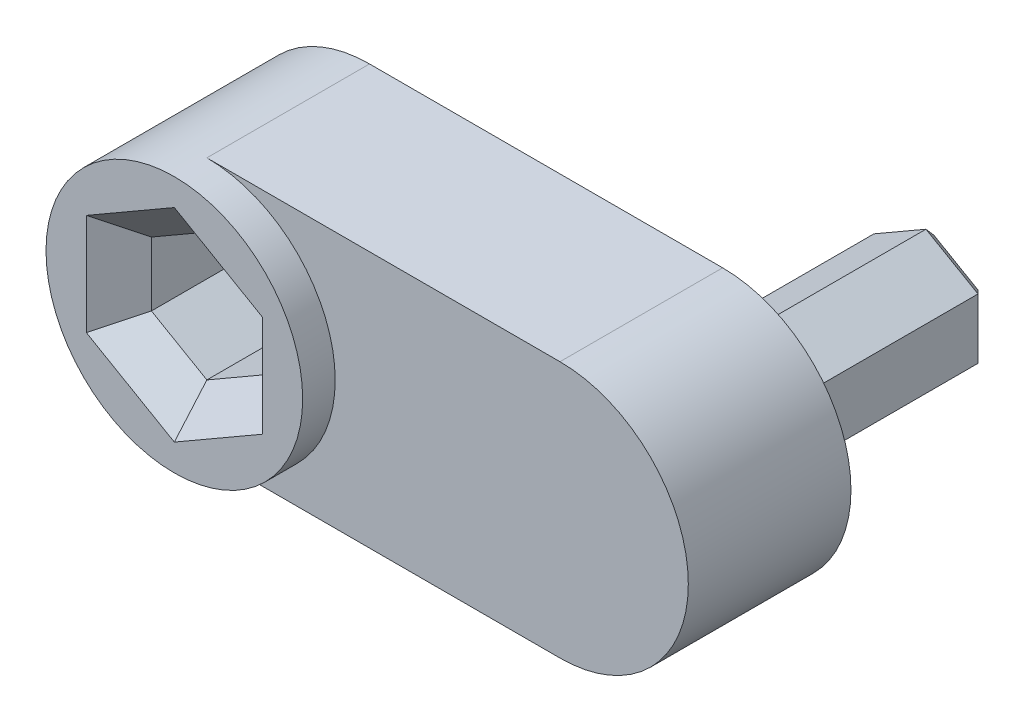
SolidWorks part; units mm, degrees
ref_plane "Plan de face" through (0, 0, 0) normal (1, 0, 0) x (0, 1, 0)
ref_plane "Plan de dessus" through (0, 0, 0) normal (0, 0, 1) x (0, 1, 0)
ref_plane "Plan de droite" through (0, 0, 0) normal (0, 1, 0) x (-1, 0, 0)
sketch "Esquisse1" plane through (0, 0, 0) normal (0, 0, 1) x (0, 1, 0)
  line L0 (0, -10.855) -> (0, 10.855) construction
  line L1 (-7.89, -10.855) -> (-7.89, 10.855)
  line L2 (7.89, -10.855) -> (7.89, 10.855)
  arc A0 (-7.89, -10.855) -> (7.89, -10.855) centre (0, -10.855) ccw
  arc A1 (7.89, 10.855) -> (-7.89, 10.855) centre (0, 10.855) ccw
  point P2 (0, 0)
  dimension "D2" = 15.78
  dimension "D1" = 21.71
extrude "Boss.-Extru.1" add sketch "Esquisse1" along normal blind 10
sketch "Esquisse3" plane through (0, 0, 0) normal (0, 0, -1) x (1, 0, 0)
  line L1 (10.855, -3.695) -> (14.055, -1.8475)
  line L2 (14.055, -1.8475) -> (14.055, 1.8475)
  line L3 (14.055, 1.8475) -> (10.855, 3.695)
  line L4 (10.855, 3.695) -> (7.655, 1.8475)
  line L5 (7.655, 1.8475) -> (7.655, -1.8475)
  line L6 (7.655, -1.8475) -> (10.855, -3.695)
  circle A0 centre (10.855, 0) radius 3.2 construction
  dimension "D1" = 6.4
extrude "Boss.-Extru.3" add sketch "Esquisse3" along normal blind 13
sketch "Esquisse2" plane through (0, 0, 10) normal (0, 0, 1) x (1, 0, 0)
  line L1 (-10.855, 3.935) -> (-14.2628, 1.9675)
  line L2 (-14.2628, 1.9675) -> (-14.2628, -1.9675)
  line L3 (-14.2628, -1.9675) -> (-10.855, -3.935)
  line L4 (-10.855, -3.935) -> (-7.4472, -1.9675)
  line L5 (-7.4472, -1.9675) -> (-7.4472, 1.9675)
  line L6 (-7.4472, 1.9675) -> (-10.855, 3.935)
  circle A0 centre (-10.855, 0) radius 3.935 construction
  circle A1 centre (-10.855, 0) radius 3.4078 construction
  dimension "D1" = 7.87
extrude "Enlèv. mat.-Extru.1" cut sketch "Esquisse2" against normal through all contours L6 L1 L2 L3 L4 L5
sketch "Esquisse4" plane through (0, 0, 10) normal (0, 0, 1) x (1, 0, 0)
  circle A0 centre (-10.855, 0) radius 7.89
  line M1 (-7.4472, 1.9675) -> (-7.4472, -1.9675)
  line M2 (-7.4472, -1.9675) -> (-10.855, -3.935)
  line M3 (-10.855, -3.935) -> (-14.2628, -1.9675)
  line M4 (-14.2628, -1.9675) -> (-14.2628, 1.9675)
  line M5 (-14.2628, 1.9675) -> (-10.855, 3.935)
  line M6 (-10.855, 3.935) -> (-7.4472, 1.9675)
  arc M9 (-10.855, 7.89) -> (-10.855, -7.89) centre (-10.855, 0) ccw
extrude "Boss.-Extru.4" add sketch "Esquisse4" along normal blind 2 contours A0 M9 M6 M1 M2 M3 M4 M5 region at (-5.4337, -5.4213, 10)
chamfer "Chanfrein1" distance 2 angle 45 6 edges at (-12.5589, 2.9512, 12) (-14.2628, 0, 12) (-12.5589, -2.9512, 12) (-9.1511, -2.9512, 12) (-7.4472, 0, 12) (-9.1511, 2.9512, 12)
chamfer "Chanfrein2" distance 0.5 angle 45 6 edges at (7.655, 0, -13) (9.255, -2.7713, -13) (12.455, -2.7713, -13) (14.055, 0, -13) (12.455, 2.7713, -13) (9.255, 2.7713, -13)
